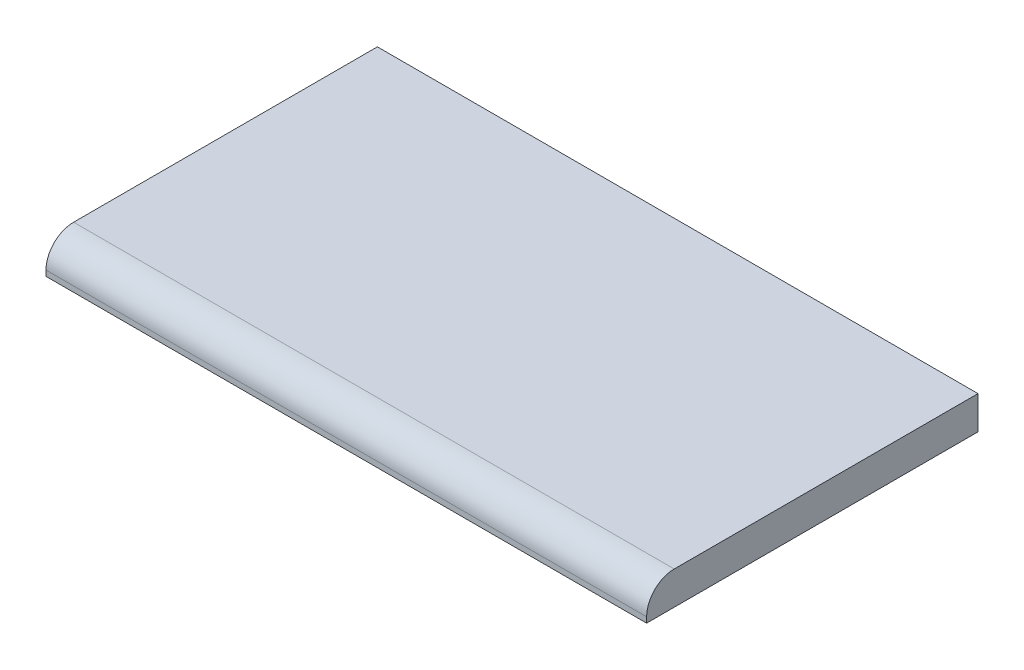
SolidWorks part; units mm, degrees
ref_plane "Front Plane" through (0, 0, 0) normal (0, 0, 1) x (1, 0, 0)
ref_plane "Top Plane" through (0, 0, 0) normal (0, 1, 0) x (1, 0, 0)
ref_plane "Right Plane" through (0, 0, 0) normal (1, 0, 0) x (0, 0, -1)
sketch "Sketch1" plane through (0, 0, 0) normal (0, 1, 0) x (1, 0, 0)
  line L0 (0, 149.352) -> (0, 150.876) construction
  line L1 (0, 0) -> (273.177, 0)
  line L2 (0, 0) -> (0, 149.352)
  line L3 (0, 149.352) -> (273.177, 149.352)
  line L4 (273.177, 0) -> (273.177, 149.352)
  line L5 (-1.524, -1.524) -> (274.701, -1.524)
  line L6 (-1.524, -1.524) -> (-1.524, 150.876)
  line L7 (-1.524, 150.876) -> (274.701, 150.876)
  line L8 (274.701, -1.524) -> (274.701, 150.876)
  line L9 (273.177, 149.352) -> (274.701, 149.352) construction
  line L10 (273.177, 0) -> (273.177, -1.524) construction
  line L11 (0, 0) -> (-1.524, 0) construction
  line L13 (0, 0) -> (273.177, 0)
  line L14 (0, 0) -> (0, 149.352)
  line L15 (0, 149.352) -> (273.177, 149.352)
  line L16 (273.177, 0) -> (273.177, 149.352)
  dimension "D1" = 1.524
  dimension "D2" = 276.225
  dimension "D3" = 152.4
extrude "Bulk-Extrude" add sketch "Sketch1" along normal blind 15.24 contours L1 L4 L3 L2 | L5 L8 L7 L6 L4 L1 L2 L3 region at (136.5885, 0, -74.676) region at (-1.2085, 0, -74.676)
fillet "Fillet1" radius 12.7 1 edges at (136.5885, 15.24, 1.524)
shell "Shell" thickness 1.524 removed face at (136.5885, 0, -74.676)
ref_plane "Mid Plane" through (136.5885, 0, 0) normal (1, 0, 0) x (0, 0, -1)
sketch "Sketch2" plane through (136.5885, 0, 0) normal (1, 0, 0) x (0, 0, -1)
  line L0 (150.876, 0) -> (154.051, 0)
  line L1 (154.051, 3.175) -> (150.876, 3.175)
  line L2 (150.876, 15.24) -> (150.876, 0) construction
  line L3 (150.876, 3.175) -> (150.876, 0)
  circle A0 centre (154.051, 0) radius 3.175
  circle A1 centre (154.051, 0) radius 1.651
  dimension "D1" = 1.524
  dimension "D2" = 6.35
extrude "Boss-Extrude3" add sketch "Sketch2" along normal mid plane 101.6 contours A1 A0 | A0 L1 L3 region at (136.5885, 2.4658, -151.5852) region at (136.5885, 2.1816, -151.8694)
